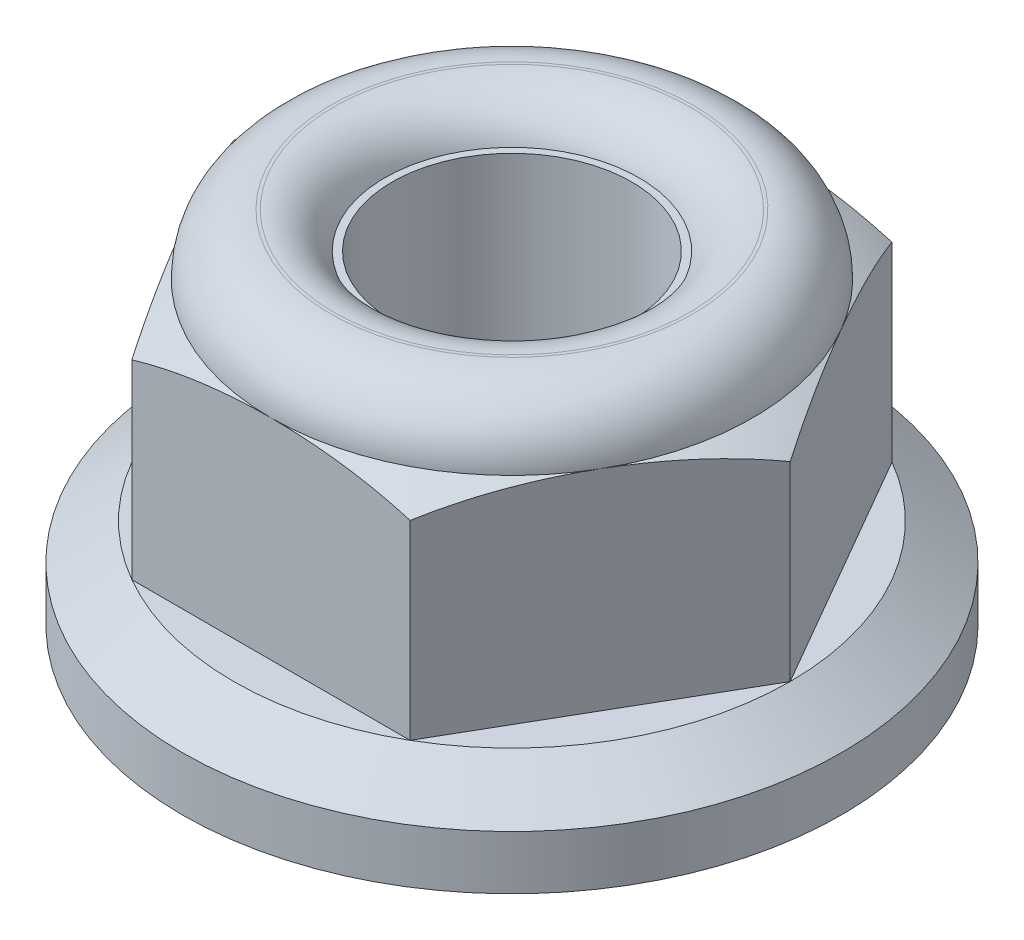
SolidWorks part; units mm, degrees
ref_plane "Front Plane" through (0, 0, 0) normal (0, 0, 1) x (1, 0, 0)
ref_plane "Top Plane" through (0, 0, 0) normal (0, 1, 0) x (1, 0, 0)
ref_plane "Right Plane" through (0, 0, 0) normal (1, 0, 0) x (0, 0, -1)
sketch "Sketch1" plane through (0, 0, 0) normal (0, 1, 0) x (1, 0, 0)
  circle A0 centre (0, 0) radius 5.5
  dimension "D1" = 11
extrude "Boss-Extrude1" add sketch "Sketch1" along normal blind 1.5
chamfer "Chamfer1" distance 0.6 angle 55 1 edges at (0, 1.5, 5.5) first distance on face at (0, 1.5, 5.5)
sketch "Sketch2" plane through (0, 1.5, 0) normal (0, 1, 0) x (1, 0, 0)
  line L1 (4.6431, 0) -> (2.3216, 4.0211)
  line L2 (2.3216, 4.0211) -> (-2.3216, 4.0211)
  line L3 (-2.3216, 4.0211) -> (-4.6431, 0)
  line L4 (-4.6431, 0) -> (-2.3216, -4.0211)
  line L5 (-2.3216, -4.0211) -> (2.3216, -4.0211)
  line L6 (2.3216, -4.0211) -> (4.6431, 0)
  circle A0 centre (0, 0) radius 4.0211 construction
extrude "Boss-Extrude2" add sketch "Sketch2" along normal blind 3.5
sketch "Sketch3" plane through (0, 5, 0) normal (0, 1, 0) x (1, 0, 0)
  circle A0 centre (0, 0) radius 4.0211
extrude "Boss-Extrude3" add sketch "Sketch3" along normal blind 1
sketch "Sketch4" plane through (0, 0, 0) normal (0, 0, 1) x (1, 0, 0)
  line L0 (0, 6) -> (0, 7.0228)
  line L1 (4.0211, 6) -> (-4.0211, 6) construction
  line L2 (4.0211, 5) -> (4.0211, 6) construction
  line L3 (2.3216, 5) -> (3.4823, 5) construction
  line L4 (6.6375, 2.7937) -> (6.6375, 7.4916)
  line L5 (6.6375, 7.4916) -> (3.0211, 7.4916)
  line L6 (3.0211, 7.4916) -> (3.0211, 6)
  arc A0 (4.0211, 5) -> (3.0211, 6) centre (3.0211, 5) ccw
  arc A1 (4.0211, 5) -> (6.6375, 2.7937) centre (1.5079, -0.6348) cw
  dimension "D1" = 1
revolve "Cut-Revolve1" cut sketch "Sketch4" angle 360 about L0
sketch "Sketch5" plane through (0, 6, 0) normal (0, 1, 0) x (1, 0, 0)
  circle A0 centre (0, 0) radius 2.1211
  circle A3 centre (0, 0) radius 3.0211 construction
  dimension "D1" = 0.9
extrude "Cut-Extrude1" cut sketch "Sketch5" against normal blind 0.6
fillet "Fillet1" radius 0.9 1 edges at (0, 6, 2.1211)
sketch "Sketch6" plane through (0, 5.4, 0) normal (0, 1, 0) x (1, 0, 0)
  circle A0 centre (0, 0) radius 2
extrude "Cut-Extrude2" cut sketch "Sketch6" against normal through all both and the other way through all
